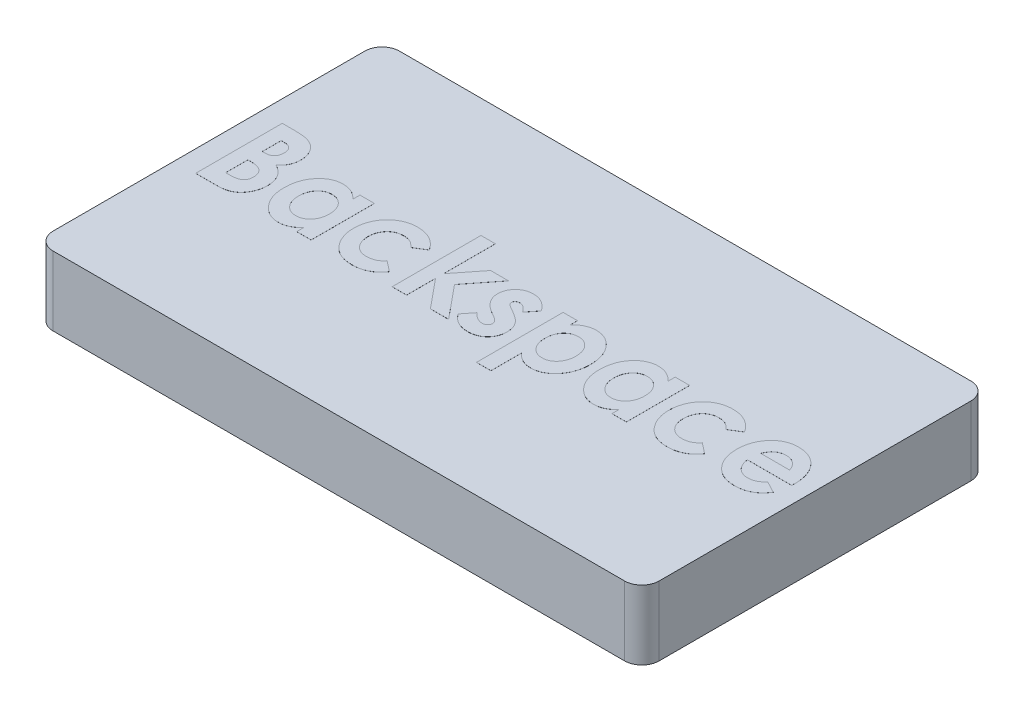
SolidWorks part; units mm, degrees
ref_plane "Front Plane" through (0, 0, 0) normal (0, 0, 1) x (1, 0, 0)
ref_plane "Top Plane" through (0, 0, 0) normal (0, 1, 0) x (1, 0, 0)
ref_plane "Right Plane" through (0, 0, 0) normal (1, 0, 0) x (0, 0, -1)
sketch "Sketch1" plane through (0, 0, 0) normal (0, 1, 0) x (1, 0, 0)
  line L0 (0, 0) -> (22.225, 0)
  line L1 (22.225, 0) -> (22.225, 12.7)
  line L2 (22.225, 12.7) -> (0, 12.7)
  line L3 (0, 12.7) -> (0, 0)
  dimension "D1" = 22.225
  dimension "D2" = 12.7
extrude "Boss-Extrude1" add sketch "Sketch1" along normal blind 2.54
fillet "Fillet1" radius 0.635 4 edges at (0, 1.27, -12.7) (22.225, 1.27, -12.7) (22.225, 1.27, 0) (0, 1.27, 0)
shell "Shell1" thickness 0.635 removed face at (11.1125, 0, -6.35)
sketch "Sketch2" plane through (0, 1.905, 0) normal (0, -1, 0) x (-1, 0, 0)
  line L0 (-0.635, 6.35) -> (-21.59, 6.35) construction
  line L1 (-0.635, 12.065) -> (-0.635, 0.635) construction
  line L2 (-21.59, 0.635) -> (-21.59, 12.065) construction
  line L3 (-11.1125, 0.635) -> (-11.1125, 12.065) construction
  line L4 (-0.635, 0.635) -> (-21.59, 0.635) construction
  line L5 (-21.59, 12.065) -> (-0.635, 12.065) construction
  circle A0 centre (-11.1125, 6.35) radius 2.54
  dimension "D1" = 5.08
extrude "Boss-Extrude2" add sketch "Sketch2" along normal up to surface (1.905 mm away) up to face at (11.1125, 0, -6.35)
sketch "Sketch3" plane through (0, 2.54, 0) normal (0, 1, 0) x (1, 0, 0)
  line L0 (0.635, 0) -> (21.59, 0) construction
  line L1 (0, 12.065) -> (0, 0.635) construction
  text T0 "<b>Backspace</b>" font "Century Gothic" height 3.175
  dimension "D1" = 5.08
  dimension "D2" = 0.4572
extrude "Boss-Extrude3" add sketch "Sketch3" along normal blind 0.0025
